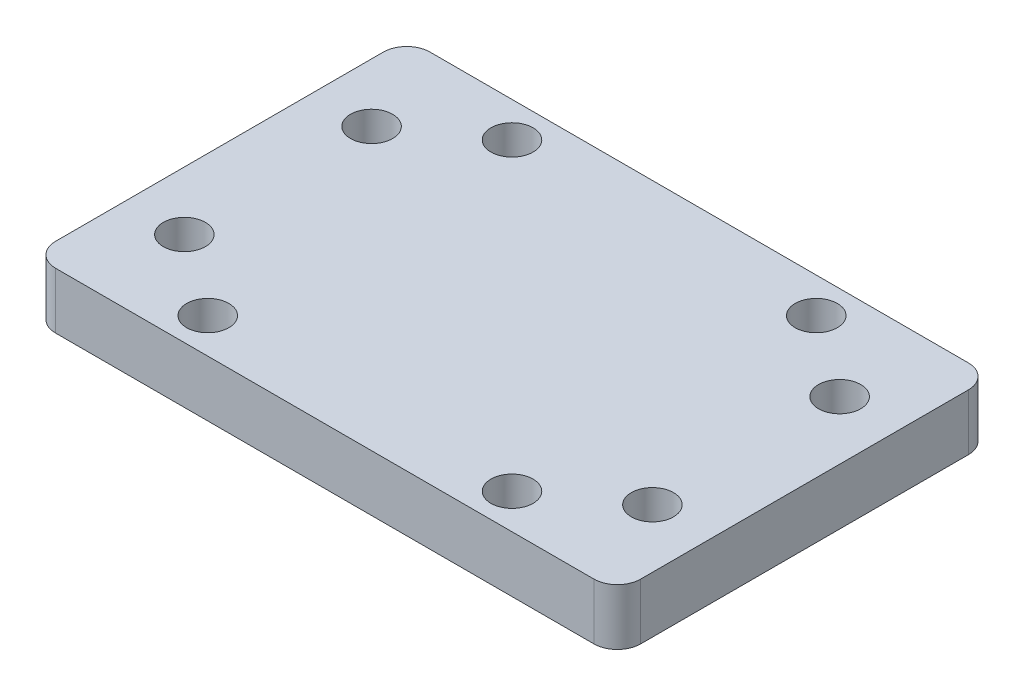
SolidWorks part; units mm, degrees
material "1.4305 (X8CrNiS18-9)"
ref_plane "Płaszczyzna przednia" through (0, 0, 0) normal (0, 0, 1) x (1, 0, 0)
ref_plane "Płaszczyzna górna" through (0, 0, 0) normal (0, 1, 0) x (1, 0, 0)
ref_plane "Płaszczyzna prawa" through (0, 0, 0) normal (1, 0, 0) x (0, 0, -1)
sketch "Szkic1" plane through (0, 0, 0) normal (0, 1, 0) x (1, 0, 0)
  line L1 (-62.5, -40) -> (62.5, -40)
  line L2 (-62.5, -40) -> (-62.5, 40)
  line L3 (-62.5, 40) -> (62.5, 40)
  line L4 (62.5, -40) -> (62.5, 40)
  line L5 (-62.5, -40) -> (62.5, 40) construction
  line L6 (-62.5, 40) -> (62.5, -40) construction
  point P0 (0, 0)
  dimension "D1" = 125
  dimension "D2" = 80
extrude "Dodanie-wyciągnięcie1" add sketch "Szkic1" along normal blind 12
fillet "Zaokrąglenie1" radius 5 4 edges at (-62.5, 6, -40) (-62.5, 6, 40) (62.5, 6, -40) (62.5, 6, 40)
sketch "Szkic2" plane through (0, 12, 0) normal (0, 1, 0) x (1, 0, 0)
  line L0 (-74.5551, 0) -> (75.9461, 0) construction
  line L1 (0, 58.9876) -> (0, -52.1774) construction
  circle A0 centre (-50, 20) radius 4
  circle A1 centre (50, 20) radius 4
  circle A2 centre (50, -20) radius 4
  circle A3 centre (-50, -20) radius 4
  dimension "D3" = 8
  dimension "D1" = 40
  dimension "D2" = 100
hole_wizard "Otwór pod śrubę M81" positions "Szkic3" profile "Szkic4" hole size "M8" standard "ISO"
sketch "Szkic3" plane through (0, 12, 0) normal (0, 1, 0) x (1, 0, 0)
  point P0 (-50, 20)
  point P3 (50, 20)
  point P6 (50, -20)
  point P9 (-50, -20)
sketch "Szkic4" plane through (-50, 12, -20) normal (1, 0, 0) x (0, 0, 1)
  line L0 (0, 0) -> (0, 18.7039)
  line L1 (0, 18.7039) -> (4.5, 16)
  line L2 (4.5, 16) -> (4.5, 0)
  line L5 (4.5, 0) -> (0, 0)
  line L10 (0, 18.7039) -> (-4.5, 16) construction
  line L11 (0, -6.35) -> (0, 107.95) construction
  dimension "Średnica otworu" = 9
  dimension "Głębokość otworu" = 16
  dimension "Kąt wiertła" = 118
sketch "Szkic5" plane through (0, 12, 0) normal (0, 1, 0) x (1, 0, 0)
  line L1 (-32.5, -32.5) -> (32.5, -32.5)
  line L2 (-32.5, -32.5) -> (-32.5, 32.5)
  line L3 (-32.5, 32.5) -> (32.5, 32.5)
  line L4 (32.5, -32.5) -> (32.5, 32.5)
  line L5 (-32.5, -32.5) -> (32.5, 32.5) construction
  line L6 (-32.5, 32.5) -> (32.5, -32.5) construction
  circle A0 centre (32.5, 32.5) radius 4
  circle A1 centre (-32.5, 32.5) radius 4
  circle A2 centre (-32.5, -32.5) radius 4
  circle A3 centre (32.5, -32.5) radius 4
  point P0 (0, 0)
  dimension "D3" = 8
  dimension "D4" = 8
  dimension "D5" = 8
  dimension "D6" = 8
  dimension "D1" = 65
  dimension "D2" = 65
hole_wizard "Otwór pod śrubę M82" positions "Szkic6" profile "Szkic7" hole size "M8" standard "ISO"
sketch "Szkic6" plane through (0, 12, 0) normal (0, 1, 0) x (1, 0, 0)
  point P0 (-32.5, 32.5)
  point P3 (32.5, 32.5)
  point P6 (32.5, -32.5)
  point P9 (-32.5, -32.5)
sketch "Szkic7" plane through (-32.5, 12, -32.5) normal (1, 0, 0) x (0, 0, 1)
  line L0 (0, 0) -> (0, 18.7039)
  line L1 (0, 18.7039) -> (4.5, 16)
  line L2 (4.5, 16) -> (4.5, 0)
  line L5 (4.5, 0) -> (0, 0)
  line L10 (0, 18.7039) -> (-4.5, 16) construction
  line L11 (0, -6.35) -> (0, 107.95) construction
  dimension "Średnica otworu" = 9
  dimension "Głębokość otworu" = 16
  dimension "Kąt wiertła" = 118
sketch "Szkic8" plane through (0, 0, 0) normal (0, -1, 0) x (1, 0, 0)
  circle A0 centre (0, 0) radius 10
  dimension "D1" = 20
extrude "Wytnij-wyciągnięcie1" cut sketch "Szkic8" against normal blind 1.5
fillet "Zaokrąglenie2" radius 1.5 1 edges at (0, 1.5, -10)
